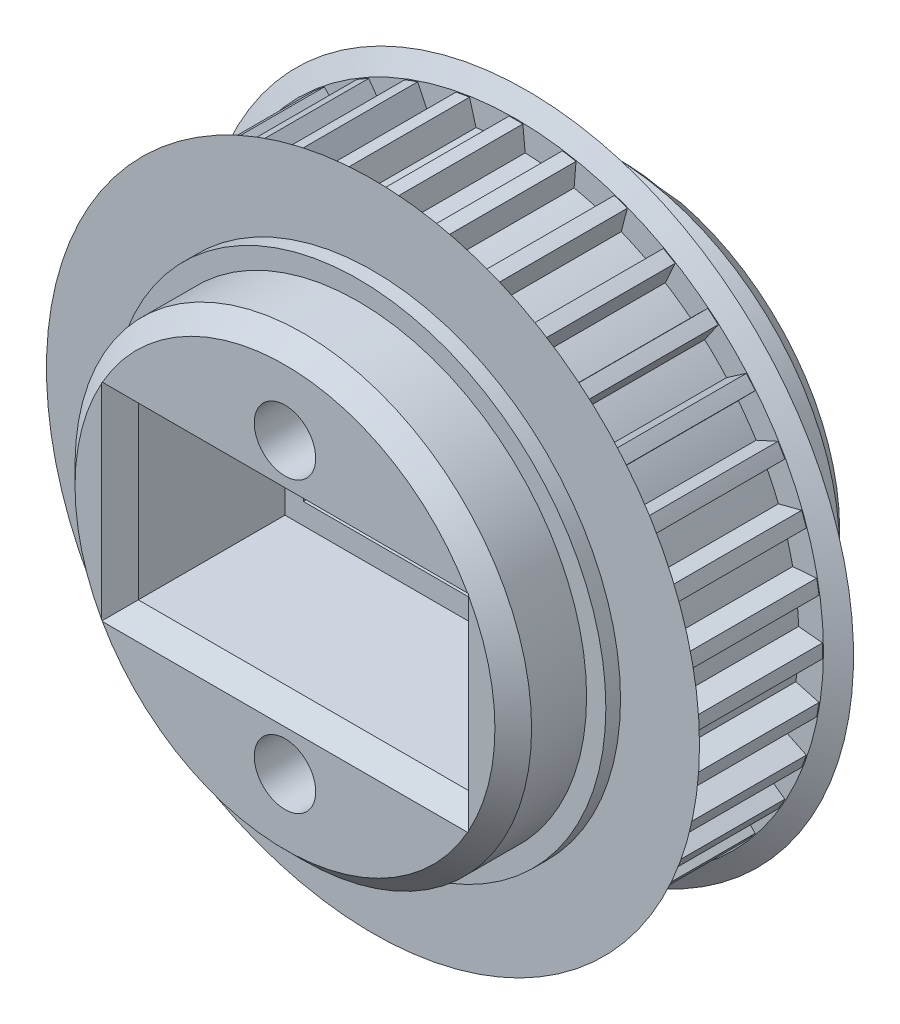
SolidWorks part; units mm, degrees
material "ABS"
ref_plane "Alzado" through (0, 0, 0) normal (0, 0, 1) x (1, 0, 0)
ref_plane "Planta" through (0, 0, 0) normal (0, 1, 0) x (1, 0, 0)
ref_plane "Vista lateral" through (0, 0, 0) normal (1, 0, 0) x (0, 0, -1)
sketch "Croquis1" plane through (0, 0, 0) normal (0, 0, 1) x (1, 0, 0)
  line L0 (0, 0) -> (0, 14.5885) construction
  line L1 (-0.375, 16.7142) -> (-0.5, 15.4103)
  line L2 (0.375, 16.7142) -> (0.5, 15.4103)
  line L3 (3.2717, 16.3952) -> (3.1684, 15.0894)
  line L4 (2.5331, 16.5254) -> (2.1836, 15.263)
  line L5 (6.069, 15.578) -> (5.7405, 14.3099)
  line L6 (5.3642, 15.8345) -> (4.8008, 14.652)
  line L7 (8.6819, 14.2874) -> (8.1382, 13.0957)
  line L8 (8.0323, 14.6624) -> (7.2721, 13.5957)
  line L9 (11.031, 12.5628) -> (10.2886, 11.4836)
  line L10 (10.4564, 13.0449) -> (9.5225, 12.1264)
  line L11 (13.0449, 10.4564) -> (12.1264, 9.5225)
  line L12 (12.5628, 11.031) -> (11.4836, 10.2886)
  line L13 (14.6624, 8.0323) -> (13.5957, 7.2721)
  line L14 (14.2874, 8.6819) -> (13.0957, 8.1382)
  line L15 (15.8345, 5.3642) -> (14.652, 4.8008)
  line L16 (15.578, 6.069) -> (14.3099, 5.7405)
  line L17 (16.5254, 2.5331) -> (15.263, 2.1836)
  line L18 (16.3952, 3.2717) -> (15.0894, 3.1684)
  line L19 (16.7142, -0.375) -> (15.4103, -0.5)
  line L20 (16.7142, 0.375) -> (15.4103, 0.5)
  line L21 (16.3952, -3.2717) -> (15.0894, -3.1684)
  line L22 (16.5254, -2.5331) -> (15.263, -2.1836)
  line L23 (15.578, -6.069) -> (14.3099, -5.7405)
  line L24 (15.8345, -5.3642) -> (14.652, -4.8008)
  line L25 (14.2874, -8.6819) -> (13.0957, -8.1382)
  line L26 (14.6624, -8.0323) -> (13.5957, -7.2721)
  line L27 (12.5628, -11.031) -> (11.4836, -10.2886)
  line L28 (13.0449, -10.4564) -> (12.1264, -9.5225)
  line L29 (10.4564, -13.0449) -> (9.5225, -12.1264)
  line L30 (11.031, -12.5628) -> (10.2886, -11.4836)
  line L31 (8.0323, -14.6624) -> (7.2721, -13.5957)
  line L32 (8.6819, -14.2874) -> (8.1382, -13.0957)
  line L33 (5.3642, -15.8345) -> (4.8008, -14.652)
  line L34 (6.069, -15.578) -> (5.7405, -14.3099)
  line L35 (2.5331, -16.5254) -> (2.1836, -15.263)
  line L36 (3.2717, -16.3952) -> (3.1684, -15.0894)
  line L37 (-0.375, -16.7142) -> (-0.5, -15.4103)
  line L38 (0.375, -16.7142) -> (0.5, -15.4103)
  line L39 (-3.2717, -16.3952) -> (-3.1684, -15.0894)
  line L40 (-2.5331, -16.5254) -> (-2.1836, -15.263)
  line L41 (-6.069, -15.578) -> (-5.7405, -14.3099)
  line L42 (-5.3642, -15.8345) -> (-4.8008, -14.652)
  line L43 (-8.6819, -14.2874) -> (-8.1382, -13.0957)
  line L44 (-8.0323, -14.6624) -> (-7.2721, -13.5957)
  line L45 (-11.031, -12.5628) -> (-10.2886, -11.4836)
  line L46 (-10.4564, -13.0449) -> (-9.5225, -12.1264)
  line L47 (-13.0449, -10.4564) -> (-12.1264, -9.5225)
  line L48 (-12.5628, -11.031) -> (-11.4836, -10.2886)
  line L49 (-14.6624, -8.0323) -> (-13.5957, -7.2721)
  line L50 (-14.2874, -8.6819) -> (-13.0957, -8.1382)
  line L51 (-15.8345, -5.3642) -> (-14.652, -4.8008)
  line L52 (-15.578, -6.069) -> (-14.3099, -5.7405)
  line L53 (-16.5254, -2.5331) -> (-15.263, -2.1836)
  line L54 (-16.3952, -3.2717) -> (-15.0894, -3.1684)
  line L55 (-16.7142, 0.375) -> (-15.4103, 0.5)
  line L56 (-16.7142, -0.375) -> (-15.4103, -0.5)
  line L57 (-16.3952, 3.2717) -> (-15.0894, 3.1684)
  line L58 (-16.5254, 2.5331) -> (-15.263, 2.1836)
  line L59 (-15.578, 6.069) -> (-14.3099, 5.7405)
  line L60 (-15.8345, 5.3642) -> (-14.652, 4.8008)
  line L61 (-14.2874, 8.6819) -> (-13.0957, 8.1382)
  line L62 (-14.6624, 8.0323) -> (-13.5957, 7.2721)
  line L63 (-12.5628, 11.031) -> (-11.4836, 10.2886)
  line L64 (-13.0449, 10.4564) -> (-12.1264, 9.5225)
  line L65 (-10.4564, 13.0449) -> (-9.5225, 12.1264)
  line L66 (-11.031, 12.5628) -> (-10.2886, 11.4836)
  line L67 (-8.0323, 14.6624) -> (-7.2721, 13.5957)
  line L68 (-8.6819, 14.2874) -> (-8.1382, 13.0957)
  line L69 (-5.3642, 15.8345) -> (-4.8008, 14.652)
  line L70 (-6.069, 15.578) -> (-5.7405, 14.3099)
  line L71 (-2.5331, 16.5254) -> (-2.1836, 15.263)
  line L72 (-3.2717, 16.3952) -> (-3.1684, 15.0894)
  arc A0 (-10.4564, 13.0449) -> (-11.031, 12.5628) centre (0, 0) ccw
  arc A1 (2.1836, 15.263) -> (0.5, 15.4103) centre (0, 0) ccw
  arc A2 (-12.5628, 11.031) -> (-13.0449, 10.4564) centre (0, 0) ccw
  arc A3 (-14.2874, 8.6819) -> (-14.6624, 8.0323) centre (0, 0) ccw
  arc A4 (-15.578, 6.069) -> (-15.8345, 5.3642) centre (0, 0) ccw
  arc A5 (-16.3952, 3.2717) -> (-16.5254, 2.5331) centre (0, 0) ccw
  arc A6 (-16.7142, 0.375) -> (-16.7142, -0.375) centre (0, 0) ccw
  arc A7 (-16.5254, -2.5331) -> (-16.3952, -3.2717) centre (0, 0) ccw
  arc A8 (-15.8345, -5.3642) -> (-15.578, -6.069) centre (0, 0) ccw
  arc A9 (-14.6624, -8.0323) -> (-14.2874, -8.6819) centre (0, 0) ccw
  arc A10 (-13.0449, -10.4564) -> (-12.5628, -11.031) centre (0, 0) ccw
  arc A11 (3.2717, 16.3952) -> (2.5331, 16.5254) centre (0, 0) ccw
  arc A12 (0.375, 16.7142) -> (-0.375, 16.7142) centre (0, 0) ccw
  arc A13 (-5.3642, 15.8345) -> (-6.069, 15.578) centre (0, 0) ccw
  arc A14 (-8.0323, 14.6624) -> (-8.6819, 14.2874) centre (0, 0) ccw
  arc A15 (-2.5331, 16.5254) -> (-3.2717, 16.3952) centre (0, 0) ccw
  arc A16 (6.069, 15.578) -> (5.3642, 15.8345) centre (0, 0) ccw
  arc A17 (8.6819, 14.2874) -> (8.0323, 14.6624) centre (0, 0) ccw
  arc A18 (11.031, 12.5628) -> (10.4564, 13.0449) centre (0, 0) ccw
  arc A19 (13.0449, 10.4564) -> (12.5628, 11.031) centre (0, 0) ccw
  arc A20 (14.6624, 8.0323) -> (14.2874, 8.6819) centre (0, 0) ccw
  arc A21 (15.8345, 5.3642) -> (15.578, 6.069) centre (0, 0) ccw
  arc A22 (16.5254, 2.5331) -> (16.3952, 3.2717) centre (0, 0) ccw
  arc A23 (16.7142, -0.375) -> (16.7142, 0.375) centre (0, 0) ccw
  arc A24 (16.3952, -3.2717) -> (16.5254, -2.5331) centre (0, 0) ccw
  arc A25 (15.578, -6.069) -> (15.8345, -5.3642) centre (0, 0) ccw
  arc A26 (8.0323, -14.6624) -> (8.6819, -14.2874) centre (0, 0) ccw
  arc A27 (5.3642, -15.8345) -> (6.069, -15.578) centre (0, 0) ccw
  arc A28 (2.5331, -16.5254) -> (3.2717, -16.3952) centre (0, 0) ccw
  arc A29 (-3.2717, -16.3952) -> (-2.5331, -16.5254) centre (0, 0) ccw
  arc A30 (-6.069, -15.578) -> (-5.3642, -15.8345) centre (0, 0) ccw
  arc A31 (-8.6819, -14.2874) -> (-8.0323, -14.6624) centre (0, 0) ccw
  arc A32 (-11.031, -12.5628) -> (-10.4564, -13.0449) centre (0, 0) ccw
  arc A33 (10.4564, -13.0449) -> (11.031, -12.5628) centre (0, 0) ccw
  arc A34 (12.5628, -11.031) -> (13.0449, -10.4564) centre (0, 0) ccw
  arc A35 (14.2874, -8.6819) -> (14.6624, -8.0323) centre (0, 0) ccw
  arc A36 (4.8008, 14.652) -> (3.1684, 15.0894) centre (0, 0) ccw
  arc A37 (7.2721, 13.5957) -> (5.7405, 14.3099) centre (0, 0) ccw
  arc A38 (-3.1684, 15.0894) -> (-4.8008, 14.652) centre (0, 0) ccw
  arc A39 (-0.5, 15.4103) -> (-2.1836, 15.263) centre (0, 0) ccw
  arc A40 (-5.7405, 14.3099) -> (-7.2721, 13.5957) centre (0, 0) ccw
  arc A41 (-8.1382, 13.0957) -> (-9.5225, 12.1264) centre (0, 0) ccw
  arc A42 (-10.2886, 11.4836) -> (-11.4836, 10.2886) centre (0, 0) ccw
  arc A43 (9.5225, 12.1264) -> (8.1382, 13.0957) centre (0, 0) ccw
  arc A44 (11.4836, 10.2886) -> (10.2886, 11.4836) centre (0, 0) ccw
  arc A45 (13.0957, 8.1382) -> (12.1264, 9.5225) centre (0, 0) ccw
  arc A46 (14.3099, 5.7405) -> (13.5957, 7.2721) centre (0, 0) ccw
  arc A47 (15.0894, 3.1684) -> (14.652, 4.8008) centre (0, 0) ccw
  arc A48 (15.4103, 0.5) -> (15.263, 2.1836) centre (0, 0) ccw
  arc A49 (15.263, -2.1836) -> (15.4103, -0.5) centre (0, 0) ccw
  arc A50 (14.652, -4.8008) -> (15.0894, -3.1684) centre (0, 0) ccw
  arc A51 (13.5957, -7.2721) -> (14.3099, -5.7405) centre (0, 0) ccw
  arc A52 (12.1264, -9.5225) -> (13.0957, -8.1382) centre (0, 0) ccw
  arc A53 (10.2886, -11.4836) -> (11.4836, -10.2886) centre (0, 0) ccw
  arc A54 (8.1382, -13.0957) -> (9.5225, -12.1264) centre (0, 0) ccw
  arc A55 (5.7405, -14.3099) -> (7.2721, -13.5957) centre (0, 0) ccw
  arc A56 (3.1684, -15.0894) -> (4.8008, -14.652) centre (0, 0) ccw
  arc A57 (0.5, -15.4103) -> (2.1836, -15.263) centre (0, 0) ccw
  arc A58 (-2.1836, -15.263) -> (-0.5, -15.4103) centre (0, 0) ccw
  arc A59 (-4.8008, -14.652) -> (-3.1684, -15.0894) centre (0, 0) ccw
  arc A60 (-7.2721, -13.5957) -> (-5.7405, -14.3099) centre (0, 0) ccw
  arc A61 (-9.5225, -12.1264) -> (-8.1382, -13.0957) centre (0, 0) ccw
  arc A62 (-11.4836, -10.2886) -> (-10.2886, -11.4836) centre (0, 0) ccw
  arc A63 (-13.0957, -8.1382) -> (-12.1264, -9.5225) centre (0, 0) ccw
  arc A64 (-14.3099, -5.7405) -> (-13.5957, -7.2721) centre (0, 0) ccw
  arc A65 (-15.0894, -3.1684) -> (-14.652, -4.8008) centre (0, 0) ccw
  arc A66 (-15.4103, -0.5) -> (-15.263, -2.1836) centre (0, 0) ccw
  arc A67 (-15.263, 2.1836) -> (-15.4103, 0.5) centre (0, 0) ccw
  arc A68 (-14.652, 4.8008) -> (-15.0894, 3.1684) centre (0, 0) ccw
  arc A69 (-13.5957, 7.2721) -> (-14.3099, 5.7405) centre (0, 0) ccw
  arc A70 (-12.1264, 9.5225) -> (-13.0957, 8.1382) centre (0, 0) ccw
  arc A71 (-0.375, -16.7142) -> (0.375, -16.7142) centre (0, 0) ccw
  circle A72 centre (0, 0) radius 2
  point P151 (0, 0)
  dimension "D1" = 1.3
  dimension "D6" = 4
  dimension "D2" = 1
  dimension "D3" = 0.75
  dimension "D5" = 1.69
  dimension "D4" = 36
extrude "Saliente-Extruir1" add sketch "Croquis1" along normal blind 7.2
sketch "Croquis2" plane through (0, 0, 7.2) normal (0, 0, 1) x (1, 0, 0)
  circle A0 centre (0, 0) radius 18.5
  circle A1 centre (0, 0) radius 2
  circle A2 centre (0, 0) radius 2 construction
  dimension "D1" = 37
extrude "Saliente-Extruir2" add sketch "Croquis2" along normal blind 0.6
sketch "Croquis3" plane through (0, 0, 7.8) normal (0, 0, 1) x (1, 0, 0)
  circle A0 centre (0, 0) radius 2
  circle A1 centre (0, 0) radius 12.45
  circle A3 centre (0, 0) radius 2 construction
  dimension "D1" = 24.9
sketch "Croquis4" plane through (0, 0, 0) normal (0, 0, -1) x (-1, 0, 0)
  circle A0 centre (0, 0) radius 2
  circle A1 centre (0, 0) radius 12.45
  circle A2 centre (0, 0) radius 2 construction
  dimension "D1" = 24.9
extrude "Saliente-Extruir4" add sketch "Croquis4" along normal blind 6.2
sketch "Croquis6" plane through (0, 0, 0) normal (0, 0, -1) x (-1, 0, 0)
  circle A0 centre (0, 0) radius 18.5
  circle A1 centre (0, 0) radius 2
  circle A2 centre (0, 0) radius 2 construction
  dimension "D1" = 37
extrude "Saliente-Extruir6" add sketch "Croquis6" along normal blind 0.6
sketch "Croquis5" plane through (0, 0, -0.6) normal (0, 0, -1) x (-1, 0, 0)
  circle A0 centre (0, 0) radius 2
  circle A1 centre (0, 0) radius 13.5
  circle A2 centre (0, 0) radius 2 construction
  dimension "D1" = 27
extrude "Saliente-Extruir5" add sketch "Croquis5" along normal blind 0.6
chamfer "Chaflán2" distance 1 angle 60 2 edges at (-18.5, 0, 0) (18.5, 0, 7.2)
extrude "Saliente-Extruir7" add sketch "Croquis3" along normal blind 4.8
chamfer "Chaflán4" distance 1 angle 45 2 edges at (-12.45, 0, -6.2) (12.45, 0, 12.6)
sketch "Croquis7" plane through (0, 0, 7.8) normal (0, 0, 1) x (1, 0, 0)
  circle A0 centre (0, 0) radius 2
  circle A1 centre (0, 0) radius 13.5
  circle A2 centre (0, 0) radius 2 construction
  dimension "D1" = 27
extrude "Saliente-Extruir8" add sketch "Croquis7" along normal blind 0.8
sketch "Croquis8" plane through (0, 0, 0) normal (0, 0, 1) x (1, 0, 0)
  line L0 (0, 0) -> (6.706, 0) construction
  line L1 (-8, 3.5) -> (8, 3.5)
  line L2 (-8, 3.5) -> (-8, -3.5)
  line L3 (-8, -3.5) -> (8, -3.5)
  line L4 (8, 3.5) -> (8, -3.5)
  line L5 (-8, 3.5) -> (8, -3.5) construction
  line L6 (-8, -3.5) -> (8, 3.5) construction
  circle A0 centre (0, 7.8756) radius 1.675
  circle A1 centre (0, -7.8756) radius 1.675
  point P0 (0, 0)
  dimension "D1" = 3.35
  dimension "D2" = 7
  dimension "D3" = 16
extrude "Cortar-Extruir1" cut sketch "Croquis8" against normal through all both and the other way through all
sketch "Croquis9" plane through (0, 0, -6.2) normal (0, 0, -1) x (-1, 0, 0)
  line L1 (2.3383, 3.8256) -> (4.6765, 7.8756)
  line L2 (4.6765, 7.8756) -> (2.3383, 11.9256)
  line L3 (2.3383, 11.9256) -> (-2.3383, 11.9256)
  line L4 (-2.3383, 11.9256) -> (-4.6765, 7.8756)
  line L5 (-4.6765, 7.8756) -> (-2.3383, 3.8256)
  line L6 (-2.3383, 3.8256) -> (2.3383, 3.8256)
  line L7 (2.3383, -11.9256) -> (4.6765, -7.8756)
  line L8 (4.6765, -7.8756) -> (2.3383, -3.8256)
  line L9 (2.3383, -3.8256) -> (-2.3383, -3.8256)
  line L10 (-2.3383, -3.8256) -> (-4.6765, -7.8756)
  line L11 (-4.6765, -7.8756) -> (-2.3383, -11.9256)
  line L12 (-2.3383, -11.9256) -> (2.3383, -11.9256)
  circle A0 centre (0, 7.8756) radius 4.05 construction
  circle A1 centre (0, -7.8756) radius 4.05 construction
  dimension "D1" = 8.1
extrude "Cortar-Extruir2" cut sketch "Croquis9" against normal blind 5.5
fillet "Redondeo1" radius 2.5 12 edges at (3.5074, -9.9006, -0.7) (3.5074, -5.8506, -0.7) (0, -3.8256, -0.7) (-3.5074, -5.8506, -0.7) (0, -11.9256, -0.7) (-3.5074, -9.9006, -0.7) (-3.5074, 5.8506, -0.7) (-3.5074, 9.9006, -0.7) (0, 11.9256, -0.7) (3.5074, 9.9006, -0.7) (3.5074, 5.8506, -0.7) (0, 3.8256, -0.7)
sketch "Croquis10" plane through (0, 0, 12.6) normal (0, 0, 1) x (1, 0, 0)
  line L1 (9, 4.65) -> (-9, 4.65)
  line L2 (9, 4.65) -> (9, -4.65)
  line L3 (9, -4.65) -> (-9, -4.65)
  line L4 (-9, 4.65) -> (-9, -4.65)
  line L5 (9, 4.65) -> (-9, -4.65) construction
  line L6 (9, -4.65) -> (-9, 4.65) construction
  point P0 (0, 0)
  dimension "D1" = 9.3
  dimension "D2" = 18
extrude "Cortar-Extruir3" cut sketch "Croquis10" against normal blind 9
chamfer "Chaflán5" distance 1 angle 45 8 edges at (-8, 0, -6.2) (0, 3.5, -6.2) (8, 0, -6.2) (0, -3.5, -6.2) (9, 0, 12.6) (0, 4.65, 12.6) (-9, 0, 12.6) (0, -4.65, 12.6)
